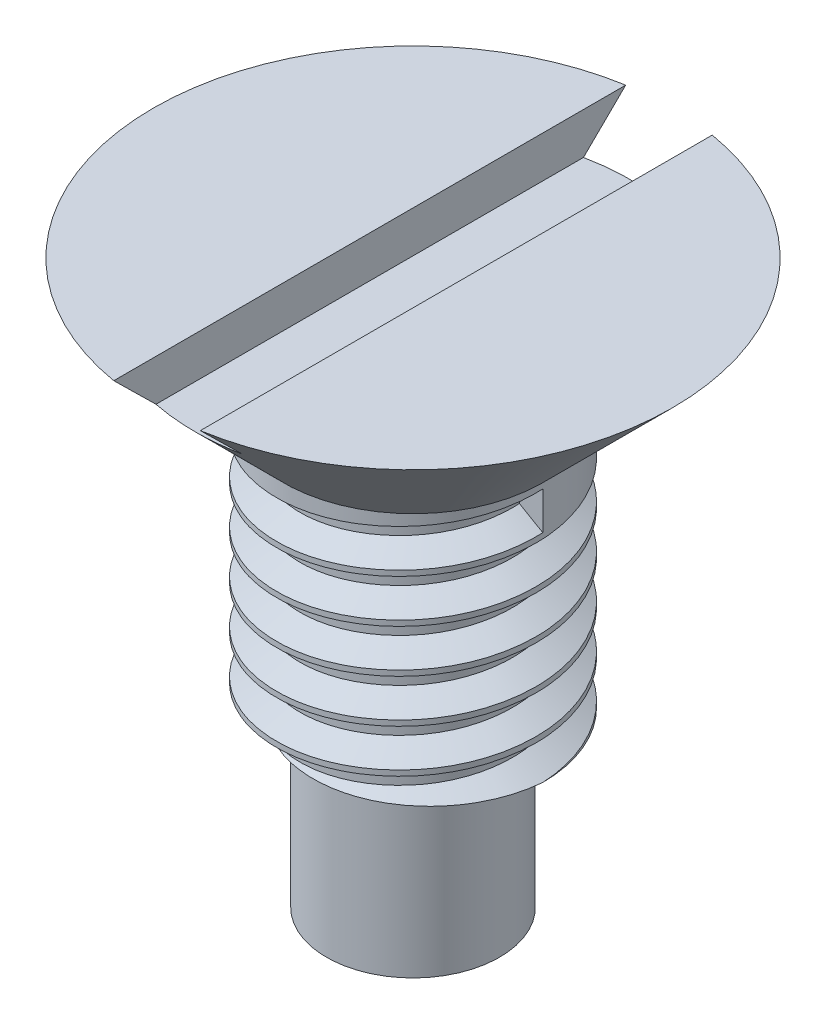
SolidWorks part; units mm, degrees
ref_plane "Front Plane" through (0, 0, 0) normal (0, 0, 1) x (1, 0, 0)
ref_plane "Top Plane" through (0, 0, 0) normal (0, 1, 0) x (1, 0, 0)
ref_plane "Right Plane" through (0, 0, 0) normal (1, 0, 0) x (0, 0, -1)
sketch "Sketch2" plane through (0, 0, 0) normal (0, 0, 1) x (1, 0, 0)
  line L0 (0, 0) -> (0, 13) construction
  line L1 (0, 0) -> (2, 0)
  line L2 (2, 0) -> (2, 4)
  line L3 (2, 4) -> (3, 4)
  line L4 (3, 4) -> (3, 10)
  line L5 (3, 10) -> (6, 13)
  line L6 (6, 13) -> (0, 13)
  line L7 (0, 0) -> (0, 13)
  dimension "D1" = 13
  dimension "D2" = 4
  dimension "D3" = 6
  dimension "D4" = 4
  dimension "D5" = 3
  dimension "D6" = 45
revolve "Revolve1" add sketch "Sketch2" angle 360 about L0
sketch "Sketch3" plane through (0, 13, 0) normal (0, 1, 0) x (1, 0, 0)
  line L1 (1, -6.6337) -> (-1, -6.6337)
  line L2 (1, -6.6337) -> (1, 6.6337)
  line L3 (1, 6.6337) -> (-1, 6.6337)
  line L4 (-1, -6.6337) -> (-1, 6.6337)
  line L5 (1, -6.6337) -> (-1, 6.6337) construction
  line L6 (1, 6.6337) -> (-1, -6.6337) construction
  point P0 (0, 0)
  dimension "D1" = 2
extrude "Cut-Extrude1" cut sketch "Sketch3" against normal blind 0.96
thread "Thread1" pitch 1 method cut profile "Thread Profile1" start angle 0, offset 2, length 7, pitch 1, diameter 6
ref_plane "Plane1" through (3, 2, 0) normal (0, 0, 1) x (1, 0, 0)
sketch "Thread Profile1" plane through (3, 2, 0) normal (0, 0, 1) x (1, 0, 0)
  line L0 (0, 0) -> (0, 1) construction
  line L11 (0, 0) -> (0, 0.875)
  line L12 (0, 0.875) -> (-0.5413, 0.5625)
  line L13 (-0.5413, 0.5625) -> (-0.5413, 0.3125)
  line L15 (-0.5413, 0.3125) -> (0, 0)
  line L17 (-0.5413, 0.4375) -> (0, 0.4375) construction
  point P2 (0, 0)
  dimension "Pitch" = 1
  dimension "Profile_Angle" = 60
  dimension "Profile_Land" = 0.25
  dimension "Profile_Height" = 0.5413
